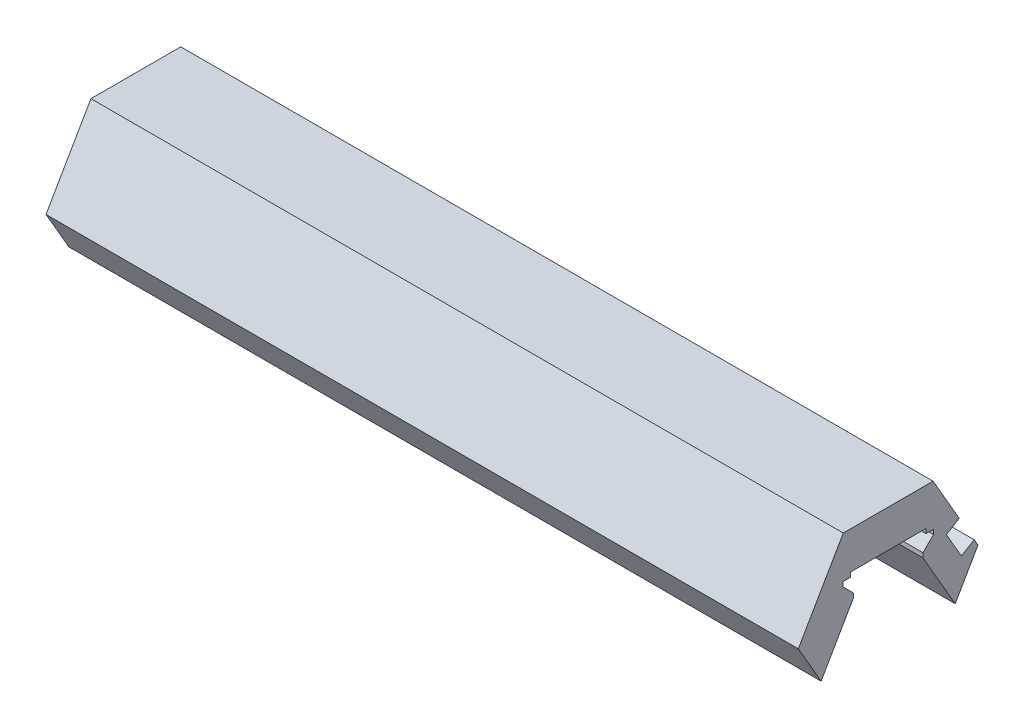
SolidWorks part; units mm, degrees
ref_plane "Front Plane" through (0, 0, 0) normal (0, 0, 1) x (1, 0, 0)
ref_plane "Top Plane" through (0, 0, 0) normal (0, 1, 0) x (1, 0, 0)
ref_plane "Right Plane" through (0, 0, 0) normal (1, 0, 0) x (0, 0, -1)
sketch "Master Design Profile" plane through (0, 0, 0) normal (1, 0, 0) x (0, 0, -1)
  line L0 (-5.05, 5.3923) -> (5.05, 5.3923)
  line L1 (12, 0) -> (6, 10.3923)
  line L2 (6, 10.3923) -> (-6, 10.3923)
  line L3 (-6, 10.3923) -> (-12, 0)
  line L4 (-12, 0) -> (-8.9579, -5.2691)
  line L5 (0, -10.3923) -> (6, -10.3923) construction
  line L6 (8.9579, -5.2691) -> (12, 0)
  line L7 (-5.05, 5.3923) -> (-5.05, 4.7923)
  line L8 (-5.05, 4.7923) -> (-6.05, 4.7923)
  line L9 (0, -28.6883) -> (0, 28.6883) construction
  line L10 (-6.05, 4.7923) -> (-6.05, 4.1923)
  line L11 (-6.05, 4.1923) -> (-4.65, 2.7923)
  line L13 (-4.65, 2.7923) -> (-4.65, 2.1923)
  line L14 (-4.65, 2.1923) -> (-8.9579, -5.2691)
  line L15 (4.65, 2.1923) -> (8.9579, -5.2691)
  line L16 (4.65, 2.7923) -> (4.65, 2.1923)
  line L17 (6.05, 4.1923) -> (4.65, 2.7923)
  line L18 (6.05, 4.7923) -> (6.05, 4.1923)
  line L19 (5.05, 4.7923) -> (6.05, 4.7923)
  line L20 (5.05, 5.3923) -> (5.05, 4.7923)
  line L21 (-9, -5.1962) -> (-6, -10.3923) construction
  line L22 (-8.9579, -5.2691) -> (-9, -5.1962) construction
  line L23 (-6, -10.3923) -> (0, -10.3923) construction
  line L24 (6, -10.3923) -> (9, -5.1962) construction
  line L25 (9, -5.1962) -> (8.9579, -5.2691) construction
  circle A0 centre (0, 0) radius 10.3923 construction
  point P15 (0, 0)
  point P16 (0, 5.3923)
  dimension "D1" = 10.1
  dimension "D2" = 0.6
  dimension "D3" = 0.6
  dimension "D4" = 1
  dimension "D5" = 135
  dimension "D6" = 2
  dimension "D7" = 5
  dimension "D8" = 210
  dimension "D9" = 0.6
  dimension "D10" = 12
sketch "LED Groove Profile Test" plane through (0, 0, 0) normal (1, 0, 0) x (0, 0, -1)
  line L0 (4.65, 2.7923) -> (4.65, 2.1923) construction
  line L1 (6.05, 4.1923) -> (4.65, 2.7923) construction
  line L2 (6.05, 4.7923) -> (6.05, 4.1923) construction
  line L3 (5.05, 4.7923) -> (6.05, 4.7923) construction
  line L4 (5.05, 5.3923) -> (5.05, 4.7923) construction
  line L5 (-5.05, 5.3923) -> (5.05, 5.3923) construction
  line L6 (-5.05, 5.3923) -> (-5.05, 4.7923) construction
  line L7 (-5.05, 4.7923) -> (-6.05, 4.7923) construction
  line L8 (-6.05, 4.7923) -> (-6.05, 4.1923) construction
  line L9 (-6.05, 4.1923) -> (-4.65, 2.7923) construction
  line L10 (-4.65, 2.7923) -> (-4.65, 2.1923) construction
  line L11 (-4.65, 2.7923) -> (-4.65, 2.1923)
  line L12 (-6.05, 4.1923) -> (-4.65, 2.7923)
  line L13 (-6.05, 4.7923) -> (-6.05, 4.1923)
  line L14 (-5.05, 4.7923) -> (-6.05, 4.7923)
  line L15 (-5.05, 5.3923) -> (-5.05, 4.7923)
  line L16 (-5.05, 5.3923) -> (5.05, 5.3923)
  line L17 (5.05, 5.3923) -> (5.05, 4.7923)
  line L18 (5.05, 4.7923) -> (6.05, 4.7923)
  line L19 (6.05, 4.7923) -> (6.05, 4.1923)
  line L20 (6.05, 4.1923) -> (4.65, 2.7923)
  line L21 (4.65, 2.7923) -> (4.65, 2.1923)
  line L22 (-4.65, 2.1923) -> (-7.5, 2.1923)
  line L23 (-7.5, 2.1923) -> (-7.5, 7.1923)
  line L24 (-7.5, 7.1923) -> (7.5, 7.1923)
  line L25 (7.5, 7.1923) -> (7.5, 2.1923)
  line L26 (7.5, 2.1923) -> (4.65, 2.1923)
  line L27 (0, -28.6883) -> (0, 28.6883) construction
  point P0 (0, 7.1923)
  dimension "D1" = 5
  dimension "D2" = 15
extrude "Boss-Extrude1" [suppressed] add sketch "LED Groove Profile Test" along normal mid plane 15
sketch "LED Segment" plane through (0, 0, 0) normal (1, 0, 0) x (0, 0, -1)
  line L0 (8.9579, -5.2691) -> (12, 0) construction
  line L1 (12, 0) -> (6, 10.3923) construction
  line L2 (6, 10.3923) -> (-6, 10.3923) construction
  line L3 (-6, 10.3923) -> (-12, 0) construction
  line L4 (-12, 0) -> (-8.9579, -5.2691) construction
  line L5 (-4.65, 2.1923) -> (-8.9579, -5.2691) construction
  line L6 (4.65, 2.1923) -> (8.9579, -5.2691) construction
  line L7 (4.65, 2.7923) -> (4.65, 2.1923) construction
  line L8 (6.05, 4.1923) -> (4.65, 2.7923) construction
  line L9 (6.05, 4.7923) -> (6.05, 4.1923) construction
  line L10 (5.05, 4.7923) -> (6.05, 4.7923) construction
  line L11 (5.05, 5.3923) -> (5.05, 4.7923) construction
  line L12 (-5.05, 5.3923) -> (5.05, 5.3923) construction
  line L13 (-5.05, 5.3923) -> (-5.05, 4.7923) construction
  line L14 (-5.05, 4.7923) -> (-6.05, 4.7923) construction
  line L15 (-6.05, 4.7923) -> (-6.05, 4.1923) construction
  line L16 (-4.65, 2.7923) -> (-4.65, 2.1923) construction
  line L17 (-6.05, 4.1923) -> (-4.65, 2.7923) construction
  line L18 (8.9579, -5.2691) -> (12, 0)
  line L19 (12, 0) -> (6, 10.3923)
  line L20 (6, 10.3923) -> (-6, 10.3923)
  line L21 (-6, 10.3923) -> (-12, 0)
  line L22 (-12, 0) -> (-8.9579, -5.2691)
  line L23 (-4.65, 2.1923) -> (-8.9579, -5.2691)
  line L24 (4.65, 2.1923) -> (8.9579, -5.2691)
  line L25 (4.65, 2.7923) -> (4.65, 2.1923)
  line L26 (6.05, 4.1923) -> (4.65, 2.7923)
  line L27 (6.05, 4.7923) -> (6.05, 4.1923)
  line L28 (5.05, 4.7923) -> (6.05, 4.7923)
  line L29 (5.05, 5.3923) -> (5.05, 4.7923)
  line L30 (-5.05, 5.3923) -> (5.05, 5.3923)
  line L31 (-5.05, 5.3923) -> (-5.05, 4.7923)
  line L32 (-5.05, 4.7923) -> (-6.05, 4.7923)
  line L33 (-6.05, 4.7923) -> (-6.05, 4.1923)
  line L34 (-4.65, 2.7923) -> (-4.65, 2.1923)
  line L35 (-6.05, 4.1923) -> (-4.65, 2.7923)
extrude "Boss-Extrude2" add sketch "LED Segment" along normal mid plane 100.5
sketch "Sketch2" plane through (0, 5.1962, -9) normal (0, 0.5, -0.866) x (-1, 0, 0)
  line L0 (50.25, -5) -> (50.25, -1)
  line L1 (50.25, -6) -> (50.25, 6) construction
  line L2 (50.25, -1) -> (-50.25, -1)
  line L3 (-50.25, -6) -> (-50.25, 6) construction
  line L4 (-50.25, -1) -> (-50.25, -5)
  line L5 (-50.25, -5) -> (50.25, -5)
  dimension "D1" = 4
  dimension "D2" = 1
extrude "Cut-Extrude1" cut sketch "Sketch2" against normal blind 2
